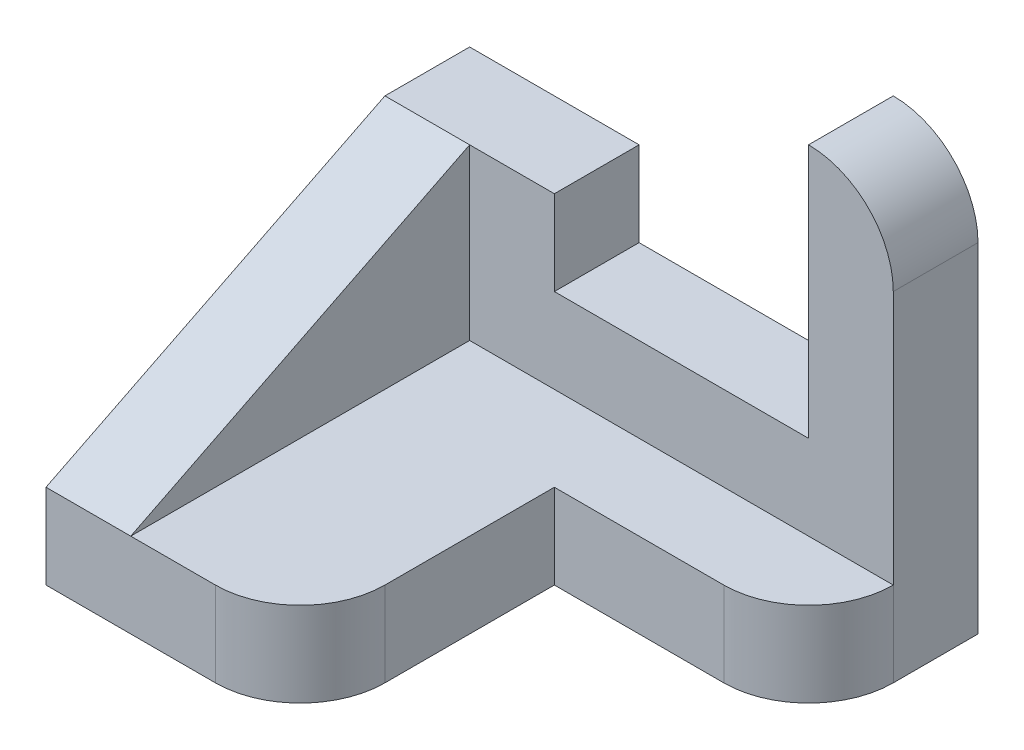
SolidWorks part; units mm, degrees
ref_plane "Ön Düzlem" through (0, 0, 0) normal (0, 0, 1) x (1, 0, 0)
ref_plane "Üst Düzlem" through (0, 0, 0) normal (0, 1, 0) x (1, 0, 0)
ref_plane "Sağ Düzlem" through (0, 0, 0) normal (1, 0, 0) x (0, 0, -1)
sketch "Sketch1" plane through (0, 0, 0) normal (0, 1, 0) x (1, 0, 0)
  line L0 (-71.2662, -36.7703) -> (-71.2662, 13.2297)
  line L1 (-71.2662, 13.2297) -> (-11.2662, 13.2297)
  line L2 (-11.2662, 13.2297) -> (-11.2662, 3.2297)
  line L3 (-21.2662, -6.7703) -> (-41.2662, -6.7703)
  line L4 (-41.2662, -6.7703) -> (-41.2662, -26.7703)
  line L5 (-51.2662, -36.7703) -> (-71.2662, -36.7703)
  arc A0 (-51.2662, -36.7703) -> (-41.2662, -26.7703) centre (-51.2662, -26.7703) ccw
  arc A1 (-21.2662, -6.7703) -> (-11.2662, 3.2297) centre (-21.2662, 3.2297) ccw
  dimension "D1" = 10
extrude "Boss-Extrude1" add sketch "Sketch1" along normal blind 10
ref_plane "Plane1" through (0, 0, -13.2297) normal (0, 0, 1) x (1, 0, 0)
sketch "Sketch2" plane through (0, 0, -13.2297) normal (0, 0, 1) x (1, 0, 0)
  line L0 (-71.2662, 10) -> (-71.2662, 30)
  line L1 (-71.2662, 30) -> (-51.2662, 30)
  line L2 (-51.2662, 30) -> (-51.2662, 20)
  line L3 (-51.2662, 20) -> (-21.2662, 20)
  line L4 (-21.2662, 20) -> (-21.2662, 50)
  line L5 (-21.2662, 50) -> (-11.2662, 50)
  line L6 (-11.2662, 50) -> (-11.2662, 10)
  line L7 (-11.2662, 10) -> (-71.2662, 10)
extrude "Boss-Extrude2" add sketch "Sketch2" along normal blind 10
fillet "Fillet1" radius 10 1 edges at (-11.2662, 50, -8.2297)
ref_plane "Plane2" through (-71.2662, 0, 0) normal (1, 0, 0) x (0, 0, -1)
sketch "Sketch3" plane through (-71.2662, 0, 0) normal (1, 0, 0) x (0, 0, -1)
  line L0 (-36.7703, 10) -> (3.2297, 30)
  line L1 (3.2297, 30) -> (3.2297, 10)
  line L2 (3.2297, 10) -> (-36.7703, 10)
extrude "Boss-Extrude3" add sketch "Sketch3" along normal blind 10
